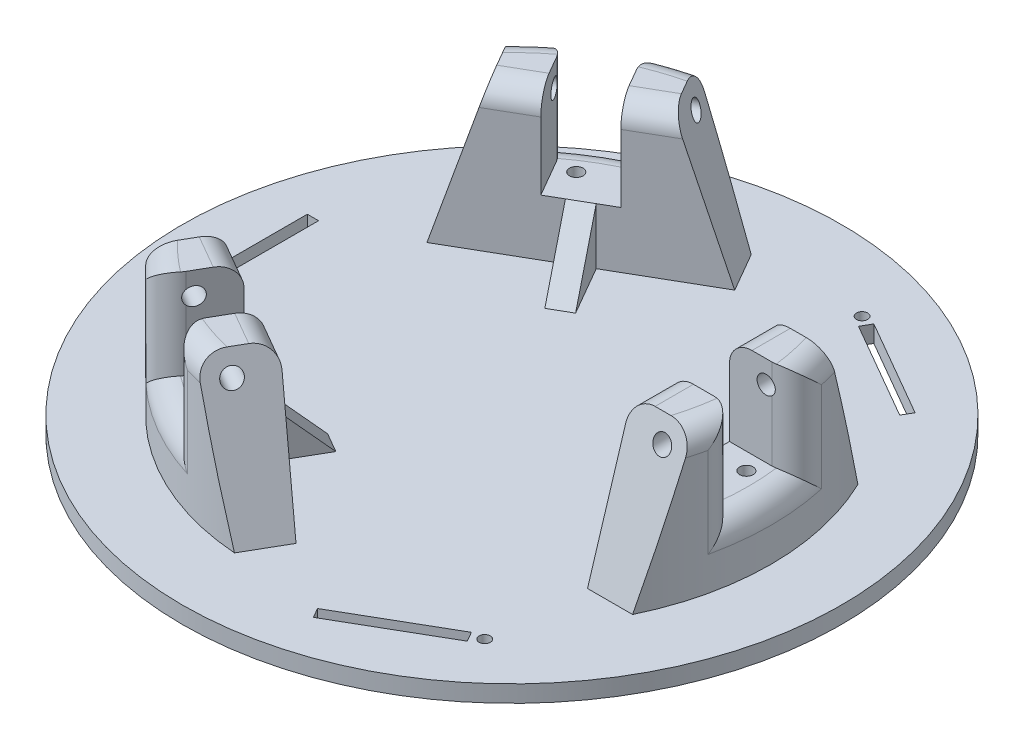
SolidWorks part; units mm, degrees
ref_plane "Front Plane" through (0, 0, 0) normal (0, 0, 1) x (1, 0, 0)
ref_plane "Top Plane" through (0, 0, 0) normal (0, 1, 0) x (1, 0, 0)
ref_plane "Right Plane" through (0, 0, 0) normal (1, 0, 0) x (0, 0, -1)
sketch "Sketch2" plane through (0, 0, 0) normal (0, 1, 0) x (1, 0, 0)
  circle A0 centre (0, 0) radius 29.255
  dimension "D1" = 58.51
extrude "Boss-Extrude1" add sketch "Sketch2" along normal blind 1.5
sketch "Sketch3" plane through (0, 0, 0) normal (0, 0, 1) x (1, 0, 0)
  line L0 (16.71, 1.5) -> (16.71, 14.5)
  line L1 (29.255, 1.5) -> (-29.255, 1.5) construction
  line L2 (16.71, 14.5) -> (20.71, 14.5)
  line L3 (20.71, 14.5) -> (20.71, 1.5)
  line L4 (20.71, 1.5) -> (16.71, 1.5)
  dimension "D1" = 13
  dimension "D2" = 4
  dimension "D3" = 16.71
extrude "Boss-Extrude2" add sketch "Sketch3" along normal mid plane 20
sketch "Sketch6" plane through (0, 1.5, 0) normal (0, 1, 0) x (1, 0, 0)
  line L0 (20.71, 10) -> (20.71, -10)
  line L1 (20.71, -10) -> (20.71, 10) construction
  line L2 (20.71, -10) -> (20.71, 10) construction
  arc A0 (20.71, 10) -> (20.71, -10) centre (-0.0023, 0) cw
  point P5 (20.71, 7.3159)
  point P9 (20.71, -5.5966)
  dimension "D1" = 23
extrude "Boss-Extrude4" add sketch "Sketch6" along normal up to surface (13 mm away) up to face at (18.71, 14.5, 0)
sketch "Sketch5" plane through (0, 0, 0) normal (0, 0, 1) x (1, 0, 0)
  line L0 (16.71, 1.5) -> (16.71, 6.5)
  line L1 (16.71, 6.5) -> (11.71, 1.5)
  line L2 (11.71, 1.5) -> (16.71, 1.5)
  line L3 (29.255, 1.5) -> (-29.255, 1.5) construction
  point P3 (0, 0)
  dimension "D1" = 5
  dimension "D2" = 11.71
extrude "Boss-Extrude3" add sketch "Sketch5" along normal mid plane 2
sketch "Sketch4" plane through (16.71, 0, 0) normal (-1, 0, 0) x (0, 0, 1)
  line L0 (10, 1.5) -> (10, 14.5)
  line L1 (10, 14.5) -> (6, 14.5)
  line L2 (-10, 14.5) -> (-10, 1.5)
  line L3 (-10, 1.5) -> (-6, 14.5)
  line L4 (10, 1.5) -> (6, 14.5)
  line L5 (2.6, 14.5) -> (-2.6, 14.5)
  line L6 (-2.6, 14.5) -> (-2.6, 6.5)
  line L7 (-2.6, 6.5) -> (2.6, 6.5)
  line L8 (2.6, 6.5) -> (2.6, 14.5)
  line L9 (2.6, 14.5) -> (-2.6, 14.5)
  line L10 (-6, 14.5) -> (-10, 14.5)
  line L11 (2.6, 14.5) -> (-2.6, 14.5)
  point P4 (0, 6.5)
  line M5 (-10, 14.5) -> (-10, 1.5)
  line M7 (10, 1.5) -> (10, 14.5)
  line M8 (10, 14.5) -> (-10, 14.5)
  dimension "D1" = 8
  dimension "D2" = 6
  dimension "D3" = 5.2
  dimension "D4" = 6
extrude "Cut-Extrude1" cut sketch "Sketch4" against normal blind 21 contours L3 L1 M5 | L4 M7 M8 | L7 L8 L5 L6 region at (16.71, 10.1667, 8.6667) region at (16.71, 10.1667, -8.6667) region at (16.71, 10.5, 0)
sketch "Sketch7" plane through (0, 6.5, 0) normal (0, 1, 0) x (1, 0, 0)
  line L0 (16.71, 2.6) -> (16.71, 1) construction
  line L1 (22.8503, 2.6) -> (16.71, 2.6) construction
  circle A0 centre (19.71, 1.1) radius 0.6
  dimension "D1" = 1.2
  dimension "D2" = 3
  dimension "D3" = 1.5
extrude "Cut-Extrude2" cut sketch "Sketch7" against normal blind 4
sketch "Sketch8" plane through (0, 0, -2.6) normal (0, 0, 1) x (1, 0, 0)
  line L0 (22.8503, 14.5) -> (16.71, 14.5) construction
  line L1 (16.71, 14.5) -> (16.71, 6.5) construction
  circle A0 centre (19.96, 12.5) radius 0.8
  dimension "D1" = 1.6
  dimension "D2" = 2
  dimension "D3" = 3.25
extrude "Cut-Extrude3" cut sketch "Sketch8" against normal through all both and the other way through all
fillet "Fillet1" radius 2 7 edges at (22.5898, 14.5, -4.3122) (22.8503, 10.5, -2.6) (22.9977, 6.5, 0) (22.8503, 10.5, 2.6) (22.5898, 14.5, 4.3122) (16.71, 14.5, -4.3) (16.71, 14.5, 4.3)
pattern_circular "CirPattern7" count 3 over 360 about axis through (0, 1.5, 0) along (0, 1, 0) of "Boss-Extrude2", "Boss-Extrude4", "Boss-Extrude3", "Cut-Extrude1", "Cut-Extrude2", "Cut-Extrude3", "Fillet1"
sketch "Sketch11" plane through (0, 1.5, 0) normal (0, 1, 0) x (1, 0, 0)
  line L0 (8.5783, 22.1828) -> (17.2386, 17.1828)
  line L1 (17.2386, 17.1828) -> (17.7386, 18.0488)
  line L2 (17.7386, 18.0488) -> (9.0783, 23.0488)
  line L3 (9.0783, 23.0488) -> (8.5783, 22.1828)
  line L4 (8.5783, 22.1828) -> (8.5001, 22.1784)
  line L5 (0.3053, 19.4713) -> (16.71, 10) construction
  line L6 (8.8283, 22.6158) -> (7.9623, 23.1158) construction
  circle A0 centre (7.9623, 23.1158) radius 0.5
  dimension "D4" = 1
  dimension "D1" = 1
  dimension "D2" = 10
  dimension "D3" = 23.5
  dimension "D5" = 1
extrude "Cut-Extrude4" cut sketch "Sketch11" against normal up to surface (1.5 mm away) contours L2 L3 L0 L1 | A0 region at (13.1585, 1.5, -20.1158) region at (7.9623, 1.5, -23.1158) up to face at (0, 0, 29.255)
pattern_circular "CirPattern8" count 3 over 360 about axis through (0, 1.5, 0) along (0, 1, 0) of "Cut-Extrude4"
